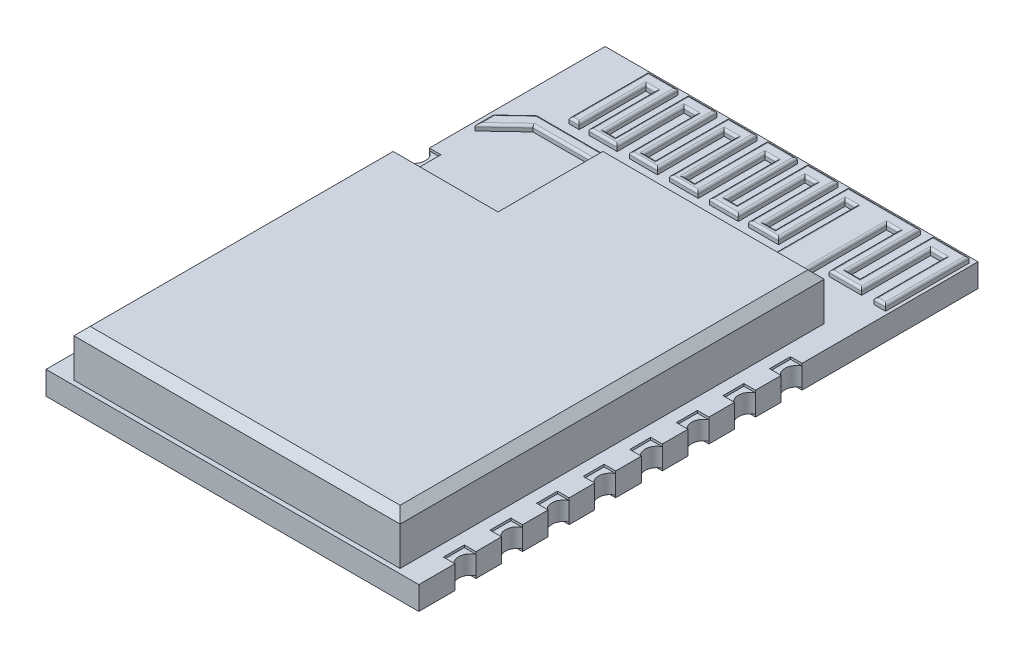
SolidWorks part; units mm, degrees
ref_plane "前基準面" through (0, 0, 0) normal (0, 0, 1) x (1, 0, 0)
ref_plane "上基準面" through (0, 0, 0) normal (0, 1, 0) x (1, 0, 0)
ref_plane "右基準面" through (0, 0, 0) normal (1, 0, 0) x (0, 0, -1)
sketch "草圖1" plane through (0, 0, 0) normal (0, 1, 0) x (1, 0, 0)
  line L5 (-8, 12) -> (8, 12)
  line L6 (-8, 12) -> (-8, -12)
  line L7 (-8, -12) -> (8, -12)
  line L8 (8, 12) -> (8, -12)
  line L9 (-8, 12) -> (8, -12) construction
  line L10 (-8, -12) -> (8, 12) construction
  point P0 (0, 0)
  dimension "D1" = 16
  dimension "24" = 24
extrude "填料-伸長1" add sketch "草圖1" along normal blind 1
sketch "草圖2" plane through (0, 1, 0) normal (0, 1, 0) x (1, 0, 0)
  line L0 (0, 0) -> (0, -5.3119)
  line L1 (-8.003, -9.55) -> (-7.503, -9.55)
  line L2 (-8.003, -9.55) -> (-8.003, -10.45)
  line L3 (-8.003, -10.45) -> (-7.503, -10.45)
  line L4 (-7.503, -9.55) -> (-7.503, -10.45)
  line L5 (8.003, -10.45) -> (7.503, -10.45)
  line L6 (7.503, -9.55) -> (7.503, -10.45)
  line L7 (8.003, -9.55) -> (7.503, -9.55)
  line L8 (8.003, -9.55) -> (8.003, -10.45)
  line L9 (-8.003, -7.55) -> (-8.003, -8.45)
  line L10 (-8.003, -7.55) -> (-7.503, -7.55)
  line L11 (-7.503, -7.55) -> (-7.503, -8.45)
  line L12 (-8.003, -8.45) -> (-7.503, -8.45)
  line L13 (-8.003, -5.55) -> (-8.003, -6.45)
  line L14 (-8.003, -5.55) -> (-7.503, -5.55)
  line L15 (-7.503, -5.55) -> (-7.503, -6.45)
  line L16 (-8.003, -6.45) -> (-7.503, -6.45)
  line L17 (-8.003, -3.55) -> (-8.003, -4.45)
  line L18 (-8.003, -3.55) -> (-7.503, -3.55)
  line L19 (-7.503, -3.55) -> (-7.503, -4.45)
  line L20 (-8.003, -4.45) -> (-7.503, -4.45)
  line L21 (-8.003, -1.55) -> (-8.003, -2.45)
  line L22 (-8.003, -1.55) -> (-7.503, -1.55)
  line L23 (-7.503, -1.55) -> (-7.503, -2.45)
  line L24 (-8.003, -2.45) -> (-7.503, -2.45)
  line L25 (-8.003, 0.45) -> (-8.003, -0.45)
  line L26 (-8.003, 0.45) -> (-7.503, 0.45)
  line L27 (-7.503, 0.45) -> (-7.503, -0.45)
  line L28 (-8.003, -0.45) -> (-7.503, -0.45)
  line L29 (-8.003, 2.45) -> (-8.003, 1.55)
  line L30 (-8.003, 2.45) -> (-7.503, 2.45)
  line L31 (-7.503, 2.45) -> (-7.503, 1.55)
  line L32 (-8.003, 1.55) -> (-7.503, 1.55)
  line L33 (-8.003, 4.45) -> (-8.003, 3.55)
  line L34 (-8.003, 4.45) -> (-7.503, 4.45)
  line L35 (-7.503, 4.45) -> (-7.503, 3.55)
  line L36 (-8.003, 3.55) -> (-7.503, 3.55)
  line L42 (8.003, -8.45) -> (7.503, -8.45)
  line L43 (7.503, -7.55) -> (7.503, -8.45)
  line L44 (8.003, -7.55) -> (7.503, -7.55)
  line L45 (8.003, -7.55) -> (8.003, -8.45)
  line L46 (8.003, -6.45) -> (7.503, -6.45)
  line L47 (7.503, -5.55) -> (7.503, -6.45)
  line L48 (8.003, -5.55) -> (7.503, -5.55)
  line L49 (8.003, -5.55) -> (8.003, -6.45)
  line L50 (8.003, -4.45) -> (7.503, -4.45)
  line L51 (7.503, -3.55) -> (7.503, -4.45)
  line L52 (8.003, -3.55) -> (7.503, -3.55)
  line L53 (8.003, -3.55) -> (8.003, -4.45)
  line L54 (8.003, -2.45) -> (7.503, -2.45)
  line L55 (7.503, -1.55) -> (7.503, -2.45)
  line L56 (8.003, -1.55) -> (7.503, -1.55)
  line L57 (8.003, -1.55) -> (8.003, -2.45)
  line L58 (8.003, -0.45) -> (7.503, -0.45)
  line L59 (7.503, 0.45) -> (7.503, -0.45)
  line L60 (8.003, 0.45) -> (7.503, 0.45)
  line L61 (8.003, 0.45) -> (8.003, -0.45)
  line L62 (8.003, 1.55) -> (7.503, 1.55)
  line L63 (7.503, 2.45) -> (7.503, 1.55)
  line L64 (8.003, 2.45) -> (7.503, 2.45)
  line L65 (8.003, 2.45) -> (8.003, 1.55)
  line L66 (8.003, 3.55) -> (7.503, 3.55)
  line L67 (7.503, 4.45) -> (7.503, 3.55)
  line L68 (8.003, 4.45) -> (7.503, 4.45)
  line L69 (8.003, 4.45) -> (8.003, 3.55)
  point P4 (-8.003, -10)
  line M6 (8, -12) -> (8, 12)
  line M8 (-8, 12) -> (-8, -12)
  dimension "D1" = 2
  dimension "D2" = 8
  dimension "D3" = 8
extrude "除料-伸長1" cut sketch "草圖2" against normal blind 0.1 contours L32 L31 L30 M8 | L28 L27 L26 M8 | L24 L23 L22 M8 | L20 L19 L18 M8 | L16 L15 L14 M8 | L12 L11 L10 M8 | L4 L1 L3 M8 | L7 L6 L5 M6 | L44 L43 L42 M6 | L48 L47 L46 M6 | L52 L51 L50 M6 | L56 L55 L54 M6 | L60 L59 L58 M6 | L68 L67 L66 M6 | L64 L63 L62 M6 | L35 L36 L33 L34 region at (-7.7515, 1, -2) region at (-7.7515, 1, 0) region at (-7.7515, 1, 2) region at (-7.7515, 1, 4) region at (-7.7515, 1, 6) region at (-7.7515, 1, 8) region at (-7.7515, 1, 10) region at (7.7515, 1, -4) region at (7.7515, 1, -2) region at (7.7515, 1, 0) region at (7.7515, 1, 2) region at (7.7515, 1, 4) region at (7.7515, 1, 6) region at (7.7515, 1, 8) region at (7.7515, 1, 10)
sketch "草圖3" plane through (0, 0, 0) normal (0, -1, 0) x (1, 0, 0)
  line L0 (7, 7.55) -> (7, 8.45)
  line L1 (8, 12) -> (8, -12) construction
  line L6 (7, 9.55) -> (8, 9.55)
  line L7 (7, 9.55) -> (7, 10.45)
  line L8 (7, 10.45) -> (8, 10.45)
  line L9 (8, 9.55) -> (8, 10.45)
  line L10 (-8, 12) -> (8, 12) construction
  line L11 (7, 7.55) -> (8, 7.55)
  line L12 (8, 7.55) -> (8, 8.45)
  line L13 (7, 8.45) -> (8, 8.45)
  line L14 (7, 5.55) -> (7, 6.45)
  line L15 (7, 5.55) -> (8, 5.55)
  line L16 (8, 5.55) -> (8, 6.45)
  line L17 (7, 6.45) -> (8, 6.45)
  line L18 (7, 3.55) -> (7, 4.45)
  line L19 (7, 3.55) -> (8, 3.55)
  line L20 (8, 3.55) -> (8, 4.45)
  line L21 (7, 4.45) -> (8, 4.45)
  line L22 (7, 1.55) -> (7, 2.45)
  line L23 (7, 1.55) -> (8, 1.55)
  line L24 (8, 1.55) -> (8, 2.45)
  line L25 (7, 2.45) -> (8, 2.45)
  line L26 (7, -0.45) -> (7, 0.45)
  line L27 (7, -0.45) -> (8, -0.45)
  line L28 (8, -0.45) -> (8, 0.45)
  line L29 (7, 0.45) -> (8, 0.45)
  line L30 (7, -2.45) -> (7, -1.55)
  line L31 (7, -2.45) -> (8, -2.45)
  line L32 (8, -2.45) -> (8, -1.55)
  line L33 (7, -1.55) -> (8, -1.55)
  line L34 (7, -4.45) -> (7, -3.55)
  line L35 (7, -4.45) -> (8, -4.45)
  line L36 (8, -4.45) -> (8, -3.55)
  line L37 (7, -3.55) -> (8, -3.55)
  line L38 (0, 0) -> (0, -2.1829)
  line L39 (-7, 10.45) -> (-8, 10.45)
  line L40 (-8, 9.55) -> (-8, 10.45)
  line L41 (-7, 9.55) -> (-8, 9.55)
  line L42 (-7, 9.55) -> (-7, 10.45)
  line L43 (-7, -4.45) -> (-8, -4.45)
  line L44 (-8, -4.45) -> (-8, -3.55)
  line L45 (-7, -3.55) -> (-8, -3.55)
  line L46 (-7, -4.45) -> (-7, -3.55)
  line L47 (-7, -2.45) -> (-8, -2.45)
  line L48 (-8, -2.45) -> (-8, -1.55)
  line L49 (-7, -1.55) -> (-8, -1.55)
  line L50 (-7, -2.45) -> (-7, -1.55)
  line L51 (-7, -0.45) -> (-8, -0.45)
  line L52 (-8, -0.45) -> (-8, 0.45)
  line L53 (-7, 0.45) -> (-8, 0.45)
  line L54 (-7, -0.45) -> (-7, 0.45)
  line L55 (-7, 1.55) -> (-8, 1.55)
  line L56 (-8, 1.55) -> (-8, 2.45)
  line L57 (-7, 2.45) -> (-8, 2.45)
  line L58 (-7, 1.55) -> (-7, 2.45)
  line L59 (-7, 3.55) -> (-8, 3.55)
  line L60 (-8, 3.55) -> (-8, 4.45)
  line L61 (-7, 4.45) -> (-8, 4.45)
  line L62 (-7, 3.55) -> (-7, 4.45)
  line L63 (-7, 5.55) -> (-8, 5.55)
  line L64 (-8, 5.55) -> (-8, 6.45)
  line L65 (-7, 6.45) -> (-8, 6.45)
  line L66 (-7, 5.55) -> (-7, 6.45)
  line L67 (-7, 7.55) -> (-8, 7.55)
  line L68 (-8, 7.55) -> (-8, 8.45)
  line L69 (-7, 8.45) -> (-8, 8.45)
  line L70 (-7, 7.55) -> (-7, 8.45)
  point P8 (8, 10)
  dimension "D1" = 2
  dimension "D2" = 0.9
  dimension "D3" = 8
extrude "除料-伸長2" cut sketch "草圖3" against normal blind 0.1 contours L67 L70 L69 L9 | L63 L66 L65 L9 | L59 L62 L61 L9 | L51 L54 L53 L9 | L47 L50 L49 L9 | L43 L46 L45 L9 | L33 L30 L31 L7 | L29 L26 L27 L7 | L25 L22 L23 L7 | L21 L18 L19 L7 | L13 L0 L11 L7 | L8 L7 L6 | L41 L40 L39 L42 | L58 L57 L56 L55 | L36 L37 L34 L35 | L17 L16 L15 L14 region at (7.5, 0, 8) region at (7.5, 0, 10) region at (7.5, 0, 4) region at (7.5, 0, 2) region at (7.5, 0, 0) region at (7.5, 0, -2) region at (-7.5, 0, -4) region at (-7.5, 0, -2) region at (-7.5, 0, 0) region at (-7.5, 0, 4) region at (-7.5, 0, 6) region at (-7.5, 0, 8)
sketch "草圖8" plane through (0, 1, 0) normal (0, 1, 0) x (1, 0, 0)
  line L0 (-8, -12) -> (8, -12) construction
  line L1 (-1, 0.6) -> (3.7, 0.6)
  line L2 (-1, 0.6) -> (-1, -4.1)
  line L3 (-1, -4.1) -> (3.7, -4.1)
  line L4 (3.7, 0.6) -> (3.7, -4.1)
  line L5 (-1, 0.6) -> (3.7, -4.1) construction
  line L6 (-1, -4.1) -> (3.7, 0.6) construction
  line L7 (-8, -2.45) -> (-8, -3.55) construction
  point P0 (1.35, -1.75)
  dimension "D1" = 7.9
  dimension "D2" = 7
  dimension "D3" = 4.7
  dimension "D4" = 4.7
extrude "除料-伸長3" cut sketch "草圖8" against normal blind 0.1
sketch "草圖12" plane through (0, 0.9, 0) normal (0, 1, 0) x (1, 0, 0)
  line L0 (-1, 0.6) -> (-1, -4.1) construction
  line L1 (-1, -4.1) -> (3.7, -4.1) construction
  circle A1 centre (-0.51, -3.65) radius 0.2
  circle A2 centre (0.42, -3.65) radius 0.2
  circle A3 centre (1.35, -3.65) radius 0.2
  circle A4 centre (2.28, -3.65) radius 0.2
  circle A5 centre (3.21, -3.65) radius 0.2
  circle A6 centre (-0.51, -2.72) radius 0.2
  circle A7 centre (0.42, -2.72) radius 0.2
  circle A8 centre (1.35, -2.72) radius 0.2
  circle A9 centre (2.28, -2.72) radius 0.2
  circle A10 centre (3.21, -2.72) radius 0.2
  circle A11 centre (-0.51, -1.79) radius 0.2
  circle A12 centre (0.42, -1.79) radius 0.2
  circle A13 centre (1.35, -1.79) radius 0.2
  circle A14 centre (2.28, -1.79) radius 0.2
  circle A15 centre (3.21, -1.79) radius 0.2
  circle A16 centre (-0.51, -0.86) radius 0.2
  circle A17 centre (0.42, -0.86) radius 0.2
  circle A18 centre (1.35, -0.86) radius 0.2
  circle A19 centre (2.28, -0.86) radius 0.2
  circle A20 centre (3.21, -0.86) radius 0.2
  circle A21 centre (-0.51, 0.07) radius 0.2
  circle A22 centre (0.42, 0.07) radius 0.2
  circle A23 centre (1.35, 0.07) radius 0.2
  circle A24 centre (2.28, 0.07) radius 0.2
  circle A25 centre (3.21, 0.07) radius 0.2
  dimension "D1" = 0.49
  dimension "D2" = 0.45
  dimension "D3" = 5
  dimension "D4" = 5
extrude "除料-伸長4" cut sketch "草圖12" against normal blind 0.1
sketch "草圖13" plane through (0, 1, 0) normal (0, 1, 0) x (1, 0, 0)
  line L5 (-1, 0.6) -> (3.7, 0.6)
  line L6 (-1, 0.6) -> (-1, -4.1)
  line L7 (-1, -4.1) -> (3.7, -4.1)
  line L8 (3.7, 0.6) -> (3.7, -4.1)
extrude "填料-伸長2" add sketch "草圖13" against normal blind 0.5
sketch "草圖15" plane through (0, 0, 0) normal (0, -1, 0) x (1, 0, 0)
  line L0 (-8, 12) -> (8, 12) construction
  line L1 (1, -0.6) -> (-3.7, -0.6)
  line L2 (1, -0.6) -> (1, 4.1)
  line L3 (1, 4.1) -> (-3.7, 4.1)
  line L4 (-3.7, -0.6) -> (-3.7, 4.1)
  line L5 (1, -0.6) -> (-3.7, 4.1) construction
  line L6 (1, 4.1) -> (-3.7, -0.6) construction
  line L7 (8, 1.55) -> (8, 0.45) construction
  point P0 (-1.35, 1.75)
  point P9 (8, 1)
  dimension "D1" = 7.9
  dimension "D2" = 7
  dimension "D3" = 4.7
  dimension "D4" = 4.7
extrude "除料-伸長5" cut sketch "草圖15" against normal blind 0.1
sketch "草圖16" plane through (0, 0, 0) normal (0, -1, 0) x (1, 0, 0)
  line L0 (1, 4.1) -> (-3.7, 4.1) construction
  line L1 (1, -0.6) -> (1, 4.1) construction
  circle A0 centre (0.51, 3.61) radius 0.2
  circle A1 centre (-0.42, 3.61) radius 0.2
  circle A2 centre (-1.35, 3.61) radius 0.2
  circle A3 centre (-2.28, 3.61) radius 0.2
  circle A4 centre (-3.21, 3.61) radius 0.2
  circle A5 centre (-3.21, 2.68) radius 0.2
  circle A6 centre (-2.28, 2.68) radius 0.2
  circle A7 centre (-1.35, 2.68) radius 0.2
  circle A8 centre (-0.42, 2.68) radius 0.2
  circle A9 centre (0.51, 2.68) radius 0.2
  circle A10 centre (-3.21, 1.75) radius 0.2
  circle A11 centre (-2.28, 1.75) radius 0.2
  circle A12 centre (-1.35, 1.75) radius 0.2
  circle A13 centre (-0.42, 1.75) radius 0.2
  circle A14 centre (0.51, 1.75) radius 0.2
  circle A15 centre (-3.21, 0.82) radius 0.2
  circle A16 centre (-2.28, 0.82) radius 0.2
  circle A17 centre (-1.35, 0.82) radius 0.2
  circle A18 centre (-0.42, 0.82) radius 0.2
  circle A19 centre (0.51, 0.82) radius 0.2
  circle A20 centre (-3.21, -0.11) radius 0.2
  circle A21 centre (-2.28, -0.11) radius 0.2
  circle A22 centre (-1.35, -0.11) radius 0.2
  circle A23 centre (-0.42, -0.11) radius 0.2
  circle A24 centre (0.51, -0.11) radius 0.2
  dimension "D1" = 0.49
  dimension "D2" = 0.49
  dimension "D3" = 5
  dimension "D4" = 5
extrude "除料-伸長6" cut sketch "草圖16" against normal blind 0.25
sketch "草圖17" plane through (0, 1, 0) normal (0, 1, 0) x (1, 0, 0)
  line L0 (-8, -12) -> (8, -12) construction
  line L5 (-2.5, 6.4) -> (7, 6.4)
  line L6 (-7, 1.4) -> (-7, -10.8)
  line L7 (-7, -10.8) -> (7, -10.8)
  line L8 (7, 6.4) -> (7, -10.8)
  line L9 (-8, 12) -> (-8, 4.45) construction
  line L10 (8, 4.45) -> (8, 12) construction
  line L16 (-2.5, 6.4) -> (-2.5, 1.9)
  line L17 (-2.5, 1.9) -> (-7, 1.9)
  line L18 (-7, 1.9) -> (-7, 1.4)
  dimension "D1" = 1.2
  dimension "D2" = 1
  dimension "D3" = 1
extrude "填料-伸長4" add sketch "草圖17" along normal blind 2
sketch "草圖18" plane through (0, 1, 0) normal (0, 1, 0) x (1, 0, 0)
  line L1 (-8, 4.45) -> (-8, 3.55)
  line L3 (-8, 2.45) -> (-8, 1.55)
  line L4 (-8, 0.45) -> (-8, -0.45)
  line L5 (-8, -1.55) -> (-8, -2.45)
  line L6 (-8, -3.55) -> (-8, -4.45)
  line L7 (-8, -5.55) -> (-8, -6.45)
  line L8 (-8, -7.55) -> (-8, -8.45)
  line L9 (-8, -9.55) -> (-8, -10.45)
  line L12 (8, 4.45) -> (8, 3.55)
  line L13 (8, 2.45) -> (8, 1.55)
  line L14 (8, 0.45) -> (8, -0.45)
  line L15 (8, -1.55) -> (8, -2.45)
  line L16 (8, -3.55) -> (8, -4.45)
  line L17 (8, -5.55) -> (8, -6.45)
  line L18 (8, -7.55) -> (8, -8.45)
  line L19 (8, -9.55) -> (8, -10.45)
  arc A0 (-8, 4.45) -> (-8, 3.55) centre (-8.2179, 4) cw
  arc A1 (-8, 2.45) -> (-8, 1.55) centre (-8.2179, 2) cw
  arc A2 (-8, 0.45) -> (-8, -0.45) centre (-8.2179, 0) cw
  arc A3 (-8, -1.55) -> (-8, -2.45) centre (-8.2179, -2) cw
  arc A4 (-8, -3.55) -> (-8, -4.45) centre (-8.2179, -4) cw
  arc A5 (-8, -5.55) -> (-8, -6.45) centre (-8.2179, -6) cw
  arc A6 (-8, -7.55) -> (-8, -8.45) centre (-8.2179, -8) cw
  arc A7 (-8, -9.55) -> (-8, -10.45) centre (-8.2179, -10) cw
  arc A8 (8, 4.45) -> (8, 3.55) centre (8.2179, 4) ccw
  arc A9 (8, 2.45) -> (8, 1.55) centre (8.2179, 2) ccw
  arc A10 (8, 0.45) -> (8, -0.45) centre (8.2179, 0) ccw
  arc A11 (8, -1.55) -> (8, -2.45) centre (8.2179, -2) ccw
  arc A12 (8, -3.55) -> (8, -4.45) centre (8.2179, -4) ccw
  arc A13 (8, -5.55) -> (8, -6.45) centre (8.2179, -6) ccw
  arc A14 (8, -7.55) -> (8, -8.45) centre (8.2179, -8) ccw
  arc A15 (8, -9.55) -> (8, -10.45) centre (8.2179, -10) ccw
  dimension "D1" = 8
extrude "除料-伸長7" cut sketch "草圖18" against normal blind 2
sketch "草圖19" plane through (0, 1, 0) normal (0, 1, 0) x (1, 0, 0)
  line L0 (-144.5969, 121.1687) -> (-19.9302, 121.1687) construction
  line L1 (-7, -10.8) -> (-7, -11.8025)
  line L2 (-7, -11.8025) -> (7, -11.8025)
  line L3 (7, -10.8) -> (7, -11.8025)
  line L4 (7, -10.8) -> (7, -11.8025)
  line L5 (-7, -10.8) -> (7, -10.8)
extrude "填料-伸長5" add sketch "草圖19" along normal up to surface (2 mm away) contours L5 L1 L2 L3 region at (0, 1, 11.3012) up to face at (-0.8333, 3, 0.8333)
sketch "草圖20" plane through (0, 1, 0) normal (0, 1, 0) x (1, 0, 0)
  line L0 (23.4441, 125.3473) -> (148.1108, 125.3473) construction
  line L1 (2.7746, 7.2994) -> (2.7746, 6.4)
  line L3 (7, 6.4) -> (-2.5, 6.4) construction
  line L4 (2.7746, 7.2994) -> (4.8557, 7.2994)
  line L5 (4.8557, 7.2994) -> (4.8557, 11.2142)
  line L6 (4.8557, 11.2142) -> (5.3615, 11.2142)
  line L7 (5.3615, 11.2142) -> (5.3615, 8.253)
  line L8 (5.3615, 8.253) -> (6.7537, 8.253)
  line L9 (6.7537, 8.253) -> (6.7537, 11.2142)
  line L10 (6.7537, 11.2142) -> (7.3504, 11.2142)
  line L11 (7.3504, 11.2142) -> (7.3504, 8.1756)
  line L12 (7.3504, 8.1756) -> (7.8586, 8.1756)
  line L13 (7.8586, 8.1756) -> (7.8586, 11.7556)
  line L14 (7.8586, 11.7556) -> (6.3117, 11.7556)
  line L15 (6.3117, 11.7556) -> (6.3117, 8.6286)
  line L16 (6.3117, 8.6286) -> (5.8587, 8.6286)
  line L17 (5.8587, 8.6286) -> (5.7703, 8.6286)
  line L18 (5.7703, 8.6286) -> (5.7703, 11.7556)
  line L19 (5.7703, 11.7556) -> (2.6765, 11.7556)
  line L20 (2.6765, 11.7556) -> (2.6765, 8.6286)
  line L21 (2.6765, 8.6286) -> (2.2345, 8.6286)
  line L22 (2.2345, 8.6286) -> (2.2345, 11.7556)
  line L23 (2.2345, 11.7556) -> (0.9417, 11.7556)
  line L24 (0.9417, 11.7556) -> (0.9417, 8.7281)
  line L25 (0.9417, 8.7281) -> (0.4887, 8.7281)
  line L26 (0.4887, 8.7281) -> (0.4887, 11.7556)
  line L27 (0.4887, 11.7556) -> (-0.782, 11.7556)
  line L28 (-0.782, 11.7556) -> (-0.782, 8.6286)
  line L29 (-0.782, 8.6286) -> (-1.235, 8.6286)
  line L30 (-1.235, 8.6286) -> (-1.235, 11.7556)
  line L31 (-1.235, 11.7556) -> (-2.4725, 11.7556)
  line L32 (-2.4725, 11.7556) -> (-2.4725, 8.6286)
  line L33 (-2.4725, 8.6286) -> (-2.9587, 8.6286)
  line L34 (-2.9587, 8.6286) -> (-2.9587, 11.7556)
  line L35 (-2.9587, 11.7556) -> (-4.1852, 11.7556)
  line L36 (-4.1852, 11.7556) -> (-4.1852, 8.6286)
  line L37 (-4.1852, 8.6286) -> (-4.6323, 8.6286)
  line L38 (-4.6323, 8.6286) -> (-4.6323, 11.7556)
  line L39 (-4.6323, 11.7556) -> (-5.9045, 11.7556)
  line L40 (-5.9045, 11.7556) -> (-5.9045, 8.3512)
  line L41 (-5.9045, 8.3512) -> (-5.4695, 8.3512)
  line L42 (-5.4695, 8.3512) -> (-5.4695, 11.2142)
  line L43 (-5.4695, 11.2142) -> (-5.0563, 11.2142)
  line L44 (-5.0563, 11.2142) -> (-5.0563, 8.3512)
  line L45 (-5.0563, 8.3512) -> (-3.8385, 8.3512)
  line L46 (-3.8385, 8.3512) -> (-3.8385, 11.2142)
  line L47 (-3.8385, 11.2142) -> (-3.3166, 11.2142)
  line L48 (-3.3166, 11.2142) -> (-3.3166, 8.3512)
  line L49 (-3.3166, 8.3512) -> (-2.1096, 8.3512)
  line L50 (-2.1096, 8.3512) -> (-2.1096, 11.2142)
  line L51 (-2.1096, 11.2142) -> (-1.5877, 11.2142)
  line L52 (-1.5877, 11.2142) -> (-1.5877, 8.3512)
  line L53 (-1.5877, 8.3512) -> (-0.3589, 8.3512)
  line L54 (-0.3589, 8.3512) -> (-0.3589, 11.2142)
  line L55 (-0.3589, 11.2142) -> (0.1195, 11.2142)
  line L56 (0.1195, 11.2142) -> (0.1195, 8.3512)
  line L57 (0.1195, 8.3512) -> (1.3591, 8.3512)
  line L58 (1.3591, 8.3512) -> (1.3591, 11.2142)
  line L59 (1.3591, 11.2142) -> (1.8049, 11.2142)
  line L60 (1.8049, 11.2142) -> (1.8049, 8.3512)
  line L61 (1.8049, 8.3512) -> (3.088, 8.3512)
  line L62 (3.088, 8.3512) -> (3.088, 11.2142)
  line L63 (3.088, 11.2142) -> (3.523, 11.2142)
  line L64 (3.523, 11.2142) -> (3.523, 7.764)
  line L65 (3.523, 7.764) -> (-6.6874, 7.764)
  line L66 (-6.6874, 7.764) -> (-7.6552, 6.8497)
  line L67 (-7.6552, 6.8497) -> (-7.6552, 6.1428)
  line L68 (-6.3743, 7.2733) -> (2.2333, 7.2733)
  line L69 (2.2333, 7.2733) -> (2.25, 6.4)
  line L70 (-6.3743, 7.2733) -> (-7.5709, 6.1428)
  line L71 (7, 6.4) -> (-2.5, 6.4) construction
  line L72 (2.25, 6.4) -> (2.7746, 6.4)
  line L73 (-7.6552, 6.1428) -> (-7.6552, 6.0749)
  line L75 (-7.5709, 6.1428) -> (-7.6552, 6.0632)
  line L76 (-7.6552, 6.0632) -> (-7.6552, 6.0749)
ref_plane "平面1" through (8, 1, -4.45) normal (0, 0, -1) x (-1, 0, 0)
extrude "填料-伸長7" add sketch "草圖20" along normal blind 0.25 contours L65 L66 L67 L73 L76 L75 L70 L68 L69 L72 L1 L4 L5 L6 L7 L8 L9 L10 L11 L12 L13 L14 L15 L16 L17 L18 L19 L20 L21 L22 L23 L24 L25 L26 L27 L28 L29 L30 L31 L32 L33 L34 L35 L36 L37 L38 L39 L40 L41 L42 L43 L44 L45 L46 L47 L48 L49 L50 L51 L52 L53 L54 L55 L56 L57 L58 L59 L60 L61 L62 L63 L64
fillet "圓角4" radius 0.1 70 edges at (2.7746, 1.125, -6.4) (2.25, 1.125, -6.4) (3.3055, 1.25, -11.2142) (3.088, 1.25, -9.7827) (2.4465, 1.25, -8.3512) (1.8049, 1.25, -9.7827) (1.582, 1.25, -11.2142) (1.3591, 1.25, -9.7827) (0.7393, 1.25, -8.3512) (0.1195, 1.25, -9.7827) (-0.1197, 1.25, -11.2142) (-0.3589, 1.25, -9.7827) (-0.9733, 1.25, -8.3512) (-1.5877, 1.25, -9.7827) (-1.8486, 1.25, -11.2142) (-2.1096, 1.25, -9.7827) (-2.7131, 1.25, -8.3512) (-3.3166, 1.25, -9.7827) (-3.5775, 1.25, -11.2142) (-3.8385, 1.25, -9.7827) (-4.4474, 1.25, -8.3512) (-5.0563, 1.25, -9.7827) (-5.2629, 1.25, -11.2142) (-5.4695, 1.25, -9.7827) (-5.687, 1.25, -8.3512) (-5.9045, 1.25, -10.0534) (-5.2684, 1.25, -11.7556) (-4.6323, 1.25, -10.1921) (-4.4087, 1.25, -8.6286) (-4.1852, 1.25, -10.1921) (-3.572, 1.25, -11.7556) (-2.9587, 1.25, -10.1921) (-2.7156, 1.25, -8.6286) (-2.4725, 1.25, -10.1921) (-1.8538, 1.25, -11.7556) (-1.235, 1.25, -10.1921) (-1.0085, 1.25, -8.6286) (-0.782, 1.25, -10.1921) (-0.1466, 1.25, -11.7556) (0.4887, 1.25, -10.2418) (0.7152, 1.25, -8.7281) (0.9417, 1.25, -10.2418) (1.5881, 1.25, -11.7556) (2.2345, 1.25, -10.1921) (2.4555, 1.25, -8.6286) (2.6765, 1.25, -10.1921) (4.2234, 1.25, -11.7556) (5.7703, 1.25, -10.1921) (6.041, 1.25, -8.6286) (6.3117, 1.25, -10.1921) (7.0852, 1.25, -11.7556) (7.8586, 1.25, -9.9656) (7.6045, 1.25, -8.1756) (7.3504, 1.25, -9.6949) (7.052, 1.25, -11.2142) (6.7537, 1.25, -9.7336) (6.0576, 1.25, -8.253) (5.3615, 1.25, -9.7336) (5.1086, 1.25, -11.2142) (4.8557, 1.25, -9.2568) (3.8151, 1.25, -7.2994) (2.7746, 1.25, -6.8497) (2.5123, 1.25, -6.4) (2.2417, 1.25, -6.8367) (-2.0705, 1.25, -7.2733) (-7.0147, 1.25, -6.6683) (-7.6552, 1.25, -6.4565) (-7.1713, 1.25, -7.3069) (-1.5822, 1.25, -7.764) (3.523, 1.25, -9.4891)
chamfer "導角1" distance 0.35 angle 45 6 edges at (0, 3, 11.8025) (-7, 3, 4.9512) (-4.75, 3, -1.9) (-2.5, 3, -4.15) (2.25, 3, -6.4) (7, 3, 2.7012)
